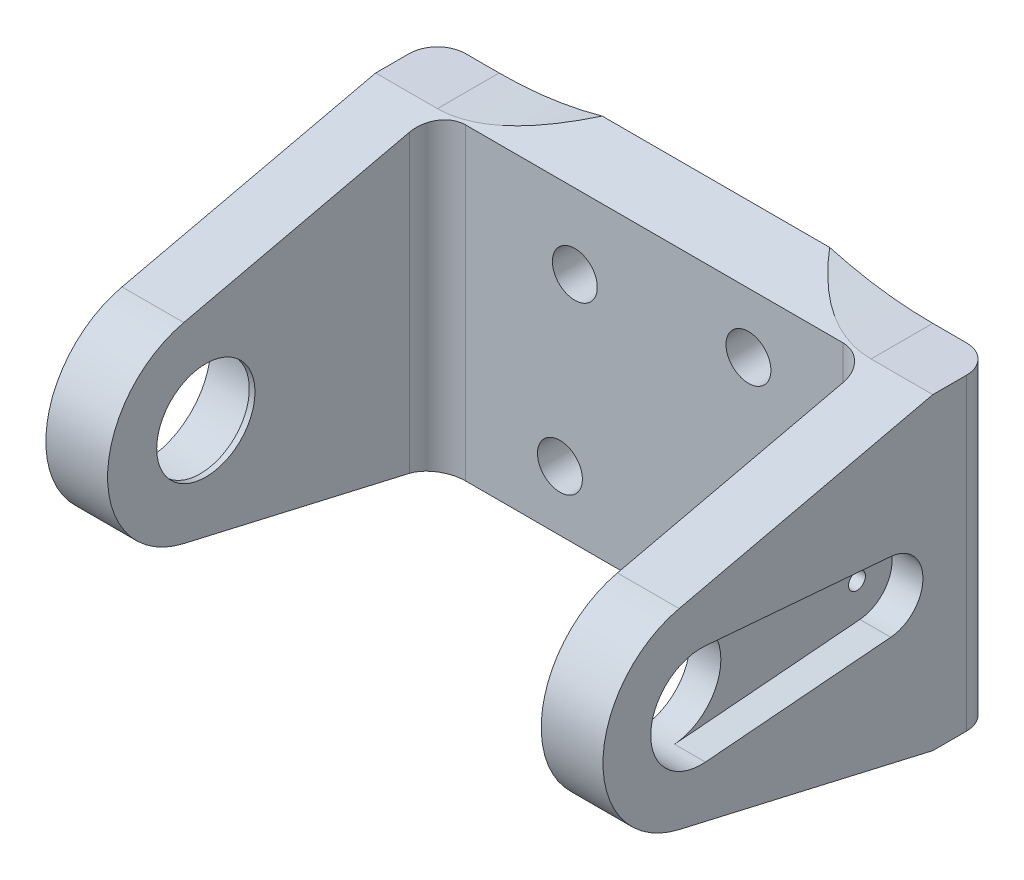
SolidWorks part; units mm, degrees
material "ABS"
ref_plane "Ön Düzlem" through (0, 0, 0) normal (0, 0, 1) x (1, 0, 0)
ref_plane "Üst Düzlem" through (0, 0, 0) normal (0, 1, 0) x (1, 0, 0)
ref_plane "Sağ Düzlem" through (0, 0, 0) normal (1, 0, 0) x (0, 0, -1)
sketch "Çizim1" plane through (0, 0, 0) normal (0, 1, 0) x (1, 0, 0)
  line L0 (-19.85, 0) -> (19.85, 0) construction
  line L1 (-19.85, -7) -> (-19.85, 20.9)
  line L2 (-19.85, -7) -> (-15.45, -7)
  line L3 (-15.45, -7) -> (-15.45, 16.5)
  line L4 (0, 0) -> (0, 16.5) construction
  line L5 (19.85, -7) -> (15.45, -7)
  line L6 (19.85, -7) -> (19.85, 20.9)
  line L7 (15.45, -7) -> (15.45, 16.5)
  line L8 (-15.45, 16.5) -> (15.45, 16.5)
  line L9 (-19.85, 20.9) -> (19.85, 20.9)
  point P4 (0, 0)
  dimension "D1" = 4.4
  dimension "D2" = 7
  dimension "D3" = 4.4
  dimension "D4" = 15.45
  dimension "D5" = 16.5
extrude "Yükseklik-Ekstrüzyon1" add sketch "Çizim1" along normal mid plane 28
sketch "Çizim2" plane through (0, 0, 0) normal (1, 0, 0) x (0, 0, -1)
  line L0 (-1.572, -6.8212) -> (20.9, -12)
  line L1 (20.9, -12) -> (20.9, 12)
  line L2 (-1.572, 6.8212) -> (20.9, 12)
  line L3 (0, 0) -> (20.9, 0) construction
  line L5 (20.9, -12) -> (20.9, -14)
  line L6 (20.9, 12) -> (20.9, 14)
  line L9 (-7, -14) -> (20.9, -14)
  line L10 (-7, 14) -> (-7, -14)
  line L11 (20.9, 14) -> (-7, 14)
  line L12 (20.9, -14) -> (20.9, 14)
  line L13 (-7, -14) -> (20.9, -14)
  line L14 (-7, 14) -> (-7, -14)
  line L15 (20.9, 14) -> (-7, 14)
  circle A0 centre (0, 0) radius 4.6 construction
  circle A1 centre (0, 0) radius 7
  point P8 (-7, 0)
  dimension "D1" = 9.2
  dimension "D3" = 24
  dimension "D5" = 0
extrude "Kes-Ekstrüzyon1" cut sketch "Çizim2" against normal through all contours A1 L14 L13 L5 L0 | A1 L2 L6 L15 L14 region at (0, -10.8054, -3.6874) region at (0, 10.8054, -3.6874)
sketch "Çizim3" plane through (0, 0, 0) normal (1, 0, 0) x (0, 0, -1)
  line L1 (20.9, -12) -> (20.9, 12) construction
  line L2 (20.9, -12) -> (20.9, -14) construction
  line L3 (-7, -14) -> (20.9, -14) construction
  line L4 (-7, 14) -> (-7, -14) construction
  line L5 (20.9, 14) -> (-7, 14) construction
  line L6 (20.9, 12) -> (20.9, 14) construction
  line L8 (-1.572, 6.8212) -> (20.9, 12)
  line L9 (20.9, -12) -> (20.9, 12)
  line L10 (20.9, -12) -> (20.9, -14)
  line L11 (-7, -14) -> (20.9, -14)
  line L12 (-7, 14) -> (-7, -14)
  line L13 (20.9, 14) -> (-7, 14)
  line L14 (20.9, 12) -> (20.9, 14)
  line L15 (-1.572, -6.8212) -> (20.9, -12)
  circle A0 centre (0, 0) radius 3.6 construction
  circle A1 centre (0, 0) radius 7
  circle A2 centre (0, 0) radius 7 construction
  dimension "D1" = 7.2
extrude "Kes-Ekstrüzyon3" cut sketch "Çizim3" along normal through all contours A1 L8 L14 L13 L12 | A1 L12 L11 L10 L15 region at (0, 10.8054, -3.6874) region at (0, -10.8054, -3.6874)
sketch "Çizim4" plane through (0, 0, -16.5) normal (0, 0, 1) x (1, 0, 0)
  line L0 (0, 0) -> (0, 14) construction
  line L1 (0, 0) -> (-14, 0) construction
  line L2 (-15.45, 10.986) -> (-19.85, 10.986)
  line L3 (-19.85, 6.8212) -> (-19.85, 12) construction
  line L4 (-19.85, 10.986) -> (-19.85, 14)
  line L5 (-19.85, 14) -> (19.85, 14)
  line L6 (-15.45, 10.986) -> (-15.45, -10.986)
  line L8 (-15.45, 10.986) -> (-15.45, -10.986)
  line L10 (15.45, 10.986) -> (19.85, 10.986)
  line L11 (19.85, 10.986) -> (19.85, 14)
  line L12 (15.45, -10.986) -> (15.45, 10.986)
  line L13 (-15.45, -10.986) -> (-19.85, -10.986)
  line L14 (-19.85, -10.986) -> (-19.85, -14)
  line L15 (-19.85, -14) -> (19.85, -14)
  line L16 (19.85, -10.986) -> (19.85, -14)
  line L17 (15.45, -10.986) -> (19.85, -10.986)
  line L22 (15.45, -10.986) -> (15.45, 10.986)
  line L23 (15.45, 10.986) -> (-15.45, 10.986)
  line L37 (15.45, 10.986) -> (-15.45, 10.986)
  line L38 (-15.45, -10.986) -> (15.45, -10.986)
  line L39 (-15.45, -10.986) -> (15.45, -10.986)
  circle A0 centre (0, 0) radius 14
  arc A1 (-15.45, 10.986) -> (-5.262, 12.9735) centre (-15.45, 38.0919) ccw
  arc A2 (-15.45, -10.986) -> (-5.262, -12.9735) centre (-15.45, -38.0919) cw
  arc A3 (15.45, -10.986) -> (5.262, -12.9735) centre (15.45, -38.0919) ccw
  arc A4 (15.45, 10.986) -> (5.262, 12.9735) centre (15.45, 38.0919) cw
  point P21 (0, 14)
  dimension "D2" = 28
  dimension "D1" = 0
extrude "Kes-Ekstrüzyon4" cut sketch "Çizim4" against normal through all contours A1 A0 | A4 A0 | A3 A0 | A2 A0 region at (-12.9763, 12.703, -16.5) region at (-12.9763, -12.703, -16.5) region at (12.9763, 12.703, -16.5) region at (12.9763, -12.703, -16.5)
sketch "Çizim6" plane through (19.85, 0, 0) normal (1, 0, 0) x (0, 0, -1)
  line L0 (0, 0) -> (13.3, 0) construction
  line L1 (13.5068, 2.4914) -> (0.2977, 3.5877)
  line L2 (13.5068, -2.4914) -> (0.2977, -3.5877)
  circle A0 centre (0, 0) radius 3.6
  circle A1 centre (13.3, 0) radius 2.5
  point P9 (15.8, 0)
  point P10 (-3.6, 0)
  dimension "D1" = 7.2
  dimension "D2" = 5
  dimension "D3" = 19.4
extrude "Kes-Ekstrüzyon6" cut sketch "Çizim6" against normal up to next contours A0 region at (19.85, 0, 0)
sketch "Çizim5" plane through (0, 0, -20.9) normal (0, 0, -1) x (-1, 0, 0)
  line L0 (0, 0) -> (0, -14) construction
  line L1 (5.6569, 5.6569) -> (-5.6569, -5.6569) construction
  line L2 (-6.7175, 6.7175) -> (6.7175, -6.7175) construction
  circle A0 centre (0, 0) radius 4
  circle A1 centre (0, 0) radius 14 construction
  circle A2 centre (-6.7175, 6.7175) radius 1.6
  circle A3 centre (-5.6569, -5.6569) radius 1.6
  circle A4 centre (6.7175, -6.7175) radius 1.6
  circle A5 centre (5.6569, 5.6569) radius 1.6
  point P10 (0, 0)
  point P13 (0, 0)
  dimension "D1" = 8
  dimension "D5" = 3.2
  dimension "D2" = 45
  dimension "D3" = 19
  dimension "D4" = 16
extrude "Kes-Ekstrüzyon5" cut sketch "Çizim5" against normal through all contours A3 | A2 | A5 | A4 region at (6.7175, 6.7175, -20.9) region at (5.6569, -5.6569, -20.9) region at (-6.7175, -6.7175, -20.9) region at (-5.6569, 5.6569, -20.9)
extrude "Kes-Ekstrüzyon7" cut sketch "Çizim6<3>" against normal blind 2.2 contours A0 L0 A1 L1 | L0 A0 L2 A1 | A1 region at (19.85, 1.6474, -6.9796) region at (19.85, -1.6474, -6.9796) region at (19.85, 1.7874, -11.6548)
sketch "Çizim6<3>" plane through (19.85, 0, 0) normal (1, 0, 0) x (0, 0, -1) same geometry as "Çizim6"
sketch "Çizim7" plane through (17.65, 0, 0) normal (1, 0, 0) x (0, 0, -1)
  circle A0 centre (13.3, 0) radius 0.6
  dimension "D1" = 13.3
  dimension "D2" = 1.2
extrude "Kes-Ekstrüzyon8" cut sketch "Çizim7" against normal up to next
sketch "Çizim9" plane through (-19.85, 0, 0) normal (-1, 0, 0) x (0, 0, 1)
  circle A0 centre (0, 0) radius 4.75
  circle A1 centre (0, 0) radius 3.5
  dimension "D1" = 9.5
  dimension "D2" = 7
extrude "Kes-Ekstrüzyon10" cut sketch "Çizim9" against normal up to next contours A1 region at (-19.85, 0, 0)
extrude "Kes-Ekstrüzyon11" cut sketch "Çizim9<3>" against normal blind 4
sketch "Çizim9<3>" plane through (-19.85, 0, 0) normal (-1, 0, 0) x (0, 0, 1) same geometry as "Çizim9"
fillet "Radyus1" radius 2 4 edges at (-19.85, 0, -20.9) (-15.45, 0, -16.5) (15.45, 0, -16.5) (19.85, 0, -20.9)
extrude "Kes-Ekstrüzyon12" cut sketch "Çizim5<3>" against normal blind 3 contours A0 region at (0, 0, -20.9)
sketch "Çizim5<3>" plane through (0, 0, -20.9) normal (0, 0, -1) x (-1, 0, 0) same geometry as "Çizim5"
chamfer "Pah1" distance 1.5 angle 45 1 edges at (-4, 0, -17.9)
sketch "Çizim10" plane through (0, 0, -16.5) normal (0, 0, 1) x (1, 0, 0)
  circle A0 centre (-5.6569, 5.6569) radius 2.75
  circle A1 centre (6.7175, 6.7175) radius 2.75
  circle A2 centre (5.6569, -5.6569) radius 2.75
  circle A3 centre (-6.7175, -6.7175) radius 2.75
  dimension "D1" = 5.5
extrude "Yükseklik-Ekstrüzyon2" [suppressed] add sketch "Çizim10" along normal blind 3
